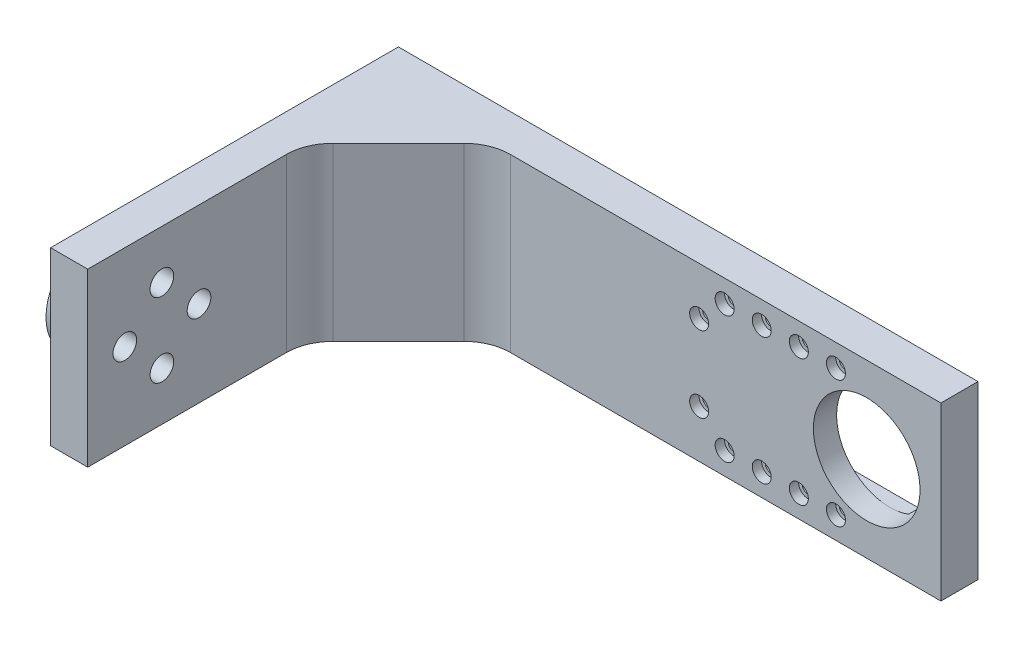
SolidWorks part; units mm, degrees
ref_plane "Front Plane" through (0, 0, 0) normal (0, 0, 1) x (1, 0, 0)
ref_plane "Top Plane" through (0, 0, 0) normal (0, 1, 0) x (1, 0, 0)
ref_plane "Right Plane" through (0, 0, 0) normal (1, 0, 0) x (0, 0, -1)
sketch "Sketch1" plane through (0, 0, 0) normal (0, 1, 0) x (1, 0, 0)
  line L0 (0, 0) -> (0, 75)
  line L1 (0, 75) -> (125, 75)
  line L2 (125, 75) -> (125, 67)
  line L3 (125, 67) -> (8, 67)
  line L4 (8, 67) -> (8, 0)
  line L5 (8, 0) -> (0, 0)
  dimension "D1" = 117
  dimension "D2" = 125
  dimension "D3" = 8
  dimension "D4" = 67
  dimension "D5" = 75
extrude "Boss-Extrude1" add sketch "Sketch1" along normal blind 37
sketch "Sketch2" plane through (0, 0, -75) normal (0, 0, -1) x (-1, 0, 0)
  line L0 (-125, 18.5) -> (-109, 18.5)
  line L1 (-125, 37) -> (-125, 0) construction
  circle A0 centre (-109, 18.5) radius 11.5
  dimension "D2" = 23
  dimension "D1" = 16
extrude "Cut-Extrude1" cut sketch "Sketch2" against normal up to next contours A0 region at (109, 7.3253, -75)
sketch "Sketch3" plane through (0, 0, -75) normal (0, 0, -1) x (-1, 0, 0)
  line L0 (-125, 32.19) -> (-102.36, 32.19)
  line L1 (-125, 37) -> (-125, 0) construction
  line L2 (-102.36, 32.19) -> (-102.36, 37)
  line L3 (-125, 37) -> (0, 37) construction
  line L4 (-125, 18.5) -> (-57.038, 18.5)
  circle A0 centre (-102.36, 32.19) radius 1.25
  circle A1 centre (-94.36, 32.19) radius 1.25
  circle A2 centre (-86.36, 32.19) radius 1.25
  circle A3 centre (-78.36, 32.19) radius 1.25
  circle A4 centre (-78.36, 4.81) radius 1.25
  circle A5 centre (-86.36, 4.81) radius 1.25
  circle A6 centre (-94.36, 4.81) radius 1.25
  circle A7 centre (-102.36, 4.81) radius 1.25
  dimension "D3" = 2.5
  dimension "D1" = 22.64
  dimension "D2" = 4.81
  dimension "D4" = 4
extrude "Cut-Extrude2" cut sketch "Sketch3" against normal up to next contours A5 | A7 | A6 | A4 | A3 | A2 | A1 | A0 region at (86.36, 4.81, -75)
sketch "Sketch4" plane through (0, 0, -75) normal (0, 0, -1) x (-1, 0, 0)
  line L0 (-113, 30) -> (-113, 7)
  line L4 (-113, 30) -> (-75, 30)
  line L5 (-75, 30) -> (-75, 7)
  line L6 (-75, 7) -> (-113, 7)
  dimension "D3" = 23
  dimension "D4" = 38
  dimension "D5" = 38
sketch "Sketch5" plane through (0, 0, 0) normal (-1, 0, 0) x (0, 0, 1)
  circle A1 centre (-16, 10.5) radius 1.25
  circle A2 centre (-24, 18.5) radius 1.25
  circle A3 centre (-16, 26.5) radius 1.25
  circle A4 centre (-8, 18.5) radius 1.25
  point P13 (-16, 18.5)
  dimension "D4" = 2.5
  dimension "D1" = 4
extrude "Cut-Extrude5" cut sketch "Sketch5" against normal up to next
sketch "Sketch6" plane through (0, 0, 0) normal (-1, 0, 0) x (0, 0, 1)
  line L0 (0, 18.5) -> (-16, 18.5)
  line L1 (0, 37) -> (0, 0) construction
  circle A0 centre (-16, 18.5) radius 11
  circle A1 centre (-16, 10.5) radius 1.25 construction
  circle A2 centre (-24, 18.5) radius 1.25 construction
  circle A3 centre (-16, 26.5) radius 1.25 construction
  circle A4 centre (-8, 18.5) radius 1.25 construction
  circle A5 centre (-16, 10.5) radius 1.25
  circle A6 centre (-24, 18.5) radius 1.25
  circle A7 centre (-16, 26.5) radius 1.25
  circle A8 centre (-8, 18.5) radius 1.25
  circle M1 centre (-8, 18.5) radius 1.25
  circle M2 centre (-16, 26.5) radius 1.25
  circle M3 centre (-24, 18.5) radius 1.25
  circle M4 centre (-16, 10.5) radius 1.25
  dimension "D2" = 22
  dimension "D1" = 16
extrude "Boss-Extrude3" add sketch "Sketch6" along normal blind 6 contours A0 M1 M3 M4 M2 region at (0, 18.5, -26.6889)
extrude "Cut-Extrude6" cut sketch "Sketch4" against normal blind 3
sketch "Sketch7" plane through (75, 0, 0) normal (1, 0, 0) x (0, 0, -1)
  line L4 (75, 7) -> (75, 30)
  line L5 (75, 30) -> (72, 30)
  line L6 (72, 30) -> (72, 7)
  line L7 (72, 7) -> (75, 7)
  line L8 (75, 7) -> (75, 30)
  line L9 (75, 30) -> (72, 30)
  line L10 (72, 30) -> (72, 7)
  line L11 (72, 7) -> (75, 7)
  dimension "D1" = 0
sketch "Sketch9" plane through (0, 0, -67) normal (0, 0, 1) x (1, 0, 0)
  circle A1 centre (78.36, 32.19) radius 2.05
  circle A2 centre (86.36, 32.19) radius 2.05
  circle A3 centre (94.36, 32.19) radius 2.05
  circle A4 centre (102.36, 32.19) radius 2.05
  circle A6 centre (78.36, 4.81) radius 2.05
  circle A7 centre (86.36, 4.81) radius 2.05
  circle A8 centre (94.36, 4.81) radius 2.05
  circle A9 centre (102.36, 4.81) radius 2.05
  dimension "D2" = 4.1
  dimension "D3" = 4.1
  dimension "D4" = 4.1
  dimension "D5" = 4.1
  dimension "D7" = 4.1
  dimension "D8" = 4.1
  dimension "D9" = 4.1
  dimension "D10" = 4.1
extrude "Cut-Extrude8" cut sketch "Sketch9" against normal blind 2
sketch "Sketch10" plane through (8, 0, 0) normal (1, 0, 0) x (0, 0, -1)
  circle A0 centre (24, 18.5) radius 2.55
  circle A1 centre (16, 10.5) radius 2.55
  circle A2 centre (8, 18.5) radius 2.55
  circle A3 centre (16, 26.5) radius 2.55
  dimension "D1" = 5.1
  dimension "D2" = 5.1
  dimension "D3" = 5.1
  dimension "D4" = 5.1
extrude "Cut-Extrude9" cut sketch "Sketch10" against normal blind 6
chamfer "Chamfer1" distance 20 angle 45 1 edges at (8, 18.5, -67)
fillet "Fillet5" radius 10 2 edges at (8, 18.5, -47) (28, 18.5, -67)
sketch "Sketch11" plane through (0, 0, -67) normal (0, 0, 1) x (1, 0, 0)
  line L0 (78.36, 4.81) -> (72.86, 4.81)
  line L1 (72.86, 4.81) -> (72.86, 10.31)
  line L2 (32.1421, 18.5) -> (74.9862, 18.5)
  line L3 (32.1421, 37) -> (32.1421, 0) construction
  circle A0 centre (72.86, 10.31) radius 1.25
  circle A1 centre (72.86, 26.69) radius 1.25
  dimension "D3" = 2.5
  dimension "D1" = 5.5
  dimension "D2" = 5.5
extrude "Cut-Extrude10" cut sketch "Sketch11" against normal up to next contours A0 | A1 region at (73.7189, 9.4511, -67) region at (72.86, 26.69, -67)
sketch "Sketch12" plane through (0, 0, -67) normal (0, 0, 1) x (1, 0, 0)
  circle A0 centre (72.86, 10.31) radius 2.05
  circle A1 centre (72.86, 26.69) radius 2.05
  dimension "D1" = 4.1
  dimension "D2" = 4.1
extrude "Cut-Extrude11" cut sketch "Sketch12" against normal blind 2
extrude "Boss-Extrude4" add sketch "Sketch7" along normal blind 0.5
